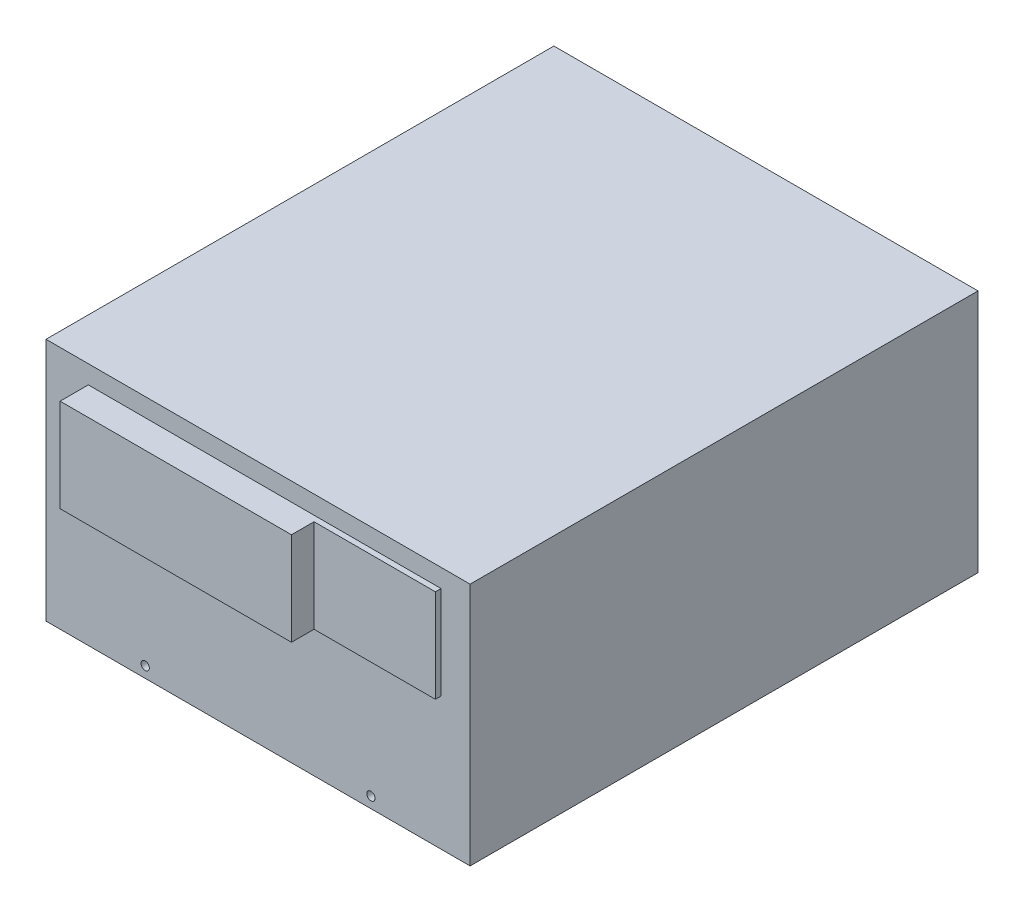
SolidWorks part; units mm, degrees
ref_plane "Front Plane" through (0, 0, 0) normal (0, 0, 1) x (1, 0, 0)
ref_plane "Top Plane" through (0, 0, 0) normal (0, 1, 0) x (1, 0, 0)
ref_plane "Right Plane" through (0, 0, 0) normal (1, 0, 0) x (0, 0, -1)
sketch "Sketch1" plane through (0, 0, 0) normal (0, 0, 1) x (1, 0, 0)
  line L0 (75.15, 86.5) -> (75.15, 0) construction
  line L1 (0, 0) -> (150.3, 0)
  line L2 (0, 0) -> (0, 86.5)
  line L3 (0, 86.5) -> (150.3, 86.5)
  line L4 (150.3, 0) -> (150.3, 86.5)
  line L5 (15, 54) -> (15, 47) construction
  line L6 (15, 54) -> (140, 54) construction
  line L7 (15, 54) -> (15, 80) construction
  line L8 (15, 80) -> (140, 80) construction
  line L9 (140, 54) -> (140, 80) construction
  line L10 (15, 47) -> (140, 47) construction
  line L11 (140, 47) -> (140, 54) construction
  line L12 (15, 47) -> (140, 47)
  line L13 (140, 47) -> (140, 80)
  line L14 (140, 80) -> (15, 80)
  line L15 (15, 80) -> (15, 47)
  line L16 (97, 80) -> (97, 47)
  circle A0 centre (35.15, 3.89) radius 1.47
  circle A1 centre (115.15, 3.89) radius 1.47
  dimension "D3" = 36.62
  dimension "D4" = 2.94
  dimension "D5" = 5.36
  dimension "D1" = 150.3
  dimension "D2" = 86.5
  dimension "D6" = 15
  dimension "D7" = 140
  dimension "D8" = 54
  dimension "D9" = 80
  dimension "D10" = 47
  dimension "D11" = 97
extrude "Boss-Extrude1" add sketch "Sketch1" against normal blind 180 contours L2 L3 L4 L1
extrude "Cut-Extrude1" cut sketch "Sketch1<3>" against normal blind 10 contours A0 | A1 region at (35.15, 3.89, 0) region at (115.15, 3.89, 0)
sketch "Sketch1<3>" plane through (0, 0, 0) normal (0, 0, 1) x (1, 0, 0) same geometry as "Sketch1"
extrude "Boss-Extrude2" add sketch "Sketch1<4>" along normal blind 10 contours L14 L15 L12 L13 region at (56, 63.5, 0)
sketch "Sketch1<4>" plane through (0, 0, 0) normal (0, 0, 1) x (1, 0, 0) same geometry as "Sketch1"
extrude "Boss-Extrude3" add sketch "Sketch1<5>" along normal blind 2 contours L14 L16 L12 L13 region at (118.5, 63.5, 0)
sketch "Sketch1<5>" plane through (0, 0, 0) normal (0, 0, 1) x (1, 0, 0) same geometry as "Sketch1"
